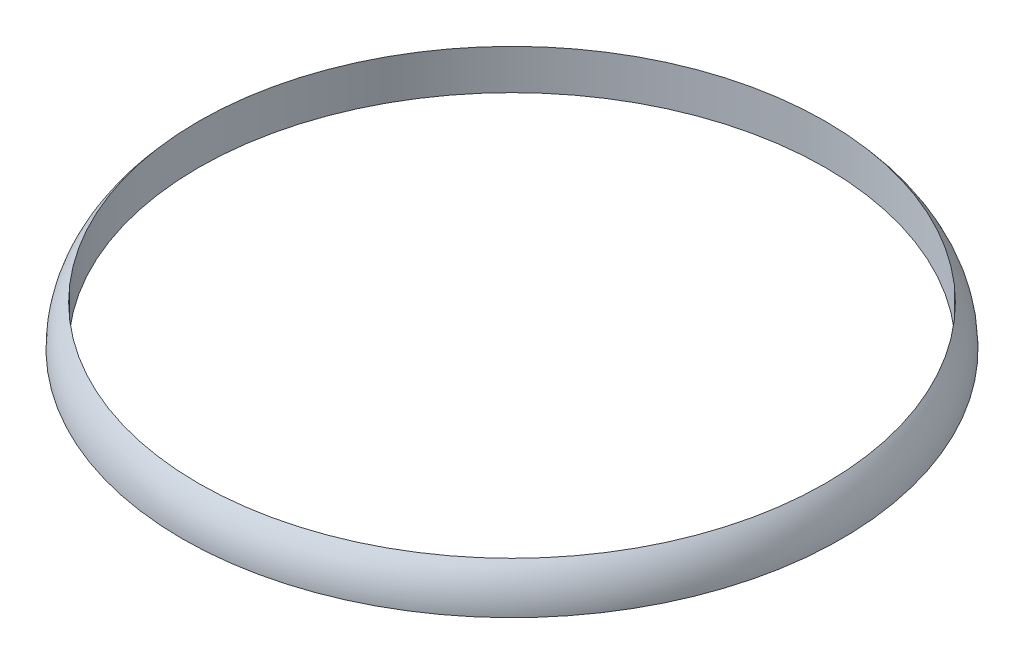
SolidWorks part; units mm, degrees
material "CFRP Filament"
ref_plane "Front Plane" through (0, 0, 0) normal (0, 0, 1) x (1, 0, 0)
ref_plane "Top Plane" through (0, 0, 0) normal (0, 1, 0) x (1, 0, 0)
ref_plane "Right Plane" through (0, 0, 0) normal (1, 0, 0) x (0, 0, -1)
sketch "Sketch1" plane through (0, 0, 0) normal (1, 0, 0) x (0, 0, -1)
  line L0 (78.2, 0) -> (78.2, 10)
  line L1 (78.2, 0) -> (82.2, 0)
  line L2 (0, 0) -> (0, 45.7169) construction
  arc A1 (82.2, 0) -> (78.2, 10) centre (67.7, 0) ccw
  dimension "D1" = 4
  dimension "D2" = 10
  dimension "D3" = 78.2
revolve "Revolve1" add sketch "Sketch1" angle 360 about L2
